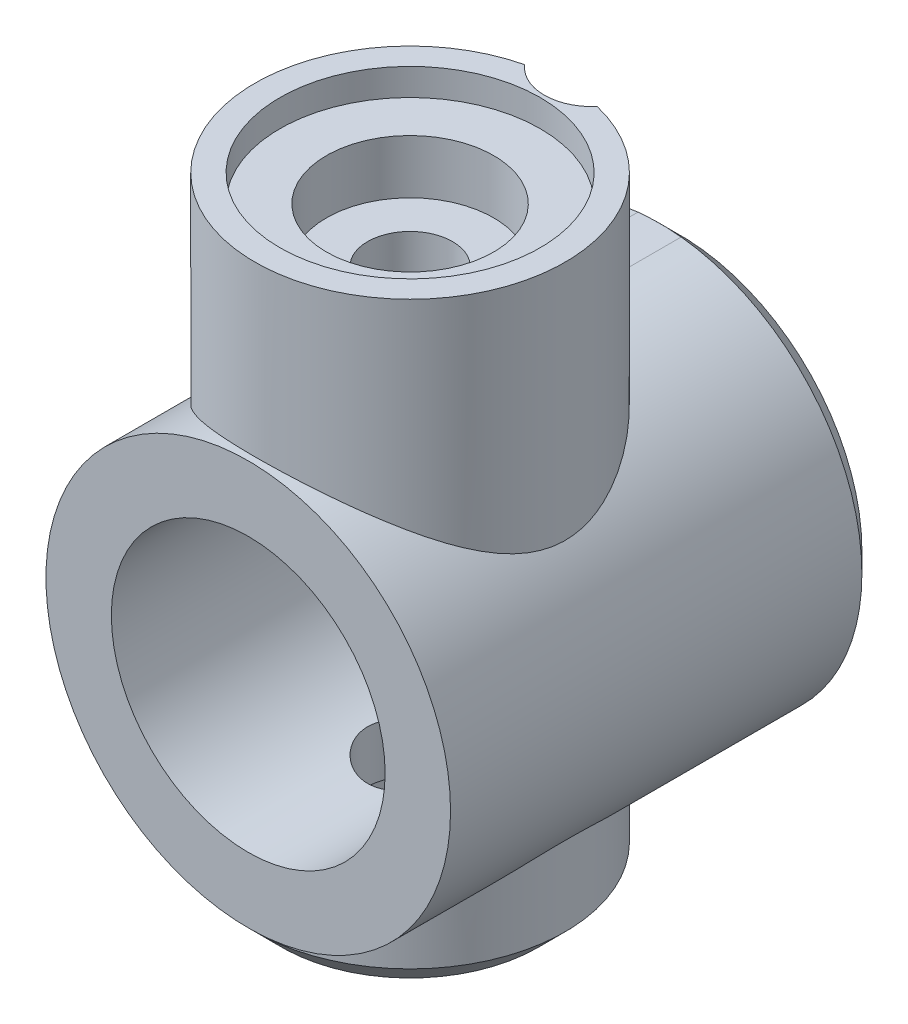
SolidWorks part; units mm, degrees
material "ABS"
ref_plane "前视基准面" through (0, 0, 0) normal (0, 0, 1) x (1, 0, 0)
ref_plane "上视基准面" through (0, 0, 0) normal (0, 1, 0) x (1, 0, 0)
ref_plane "右视基准面" through (0, 0, 0) normal (1, 0, 0) x (0, 0, -1)
other "Configuration Table"
sketch "草图1" plane through (0, 0, 0) normal (0, 1, 0) x (1, 0, 0)
  line L0 (0, 0) -> (55, 0)
  line L1 (0, 0) -> (0, -7)
  line L2 (55, 0) -> (55, -7)
  arc A0 (0, -7) -> (55, -7) centre (27.5, -7) ccw
  dimension "D1" = 55
  dimension "D2" = 7
  dimension "D3" = 7
extrude "凸台-拉伸1" add sketch "草图1" along normal blind 45
sketch "草图5" plane through (0, 0, 0) normal (0, 0, -1) x (-1, 0, 0)
  line L0 (-55, 45) -> (0, 0) construction
  line L1 (-55, 0) -> (0, 45) construction
  circle A0 centre (-27.5, 22.5) radius 7.9
  dimension "D1" = 15.8
extrude "凸台-拉伸3" add sketch "草图5" along normal blind 45
chamfer "倒角5" distance 8 angle 45 6 edges at (0, 45, 3.5) (55, 45, 3.5) (27.5, 45, 34.5) (0, 0, 3.5) (55, 0, 3.5) (27.5, 0, 34.5)
chamfer "倒角6" distance 2 angle 45 8 edges at (4, 4, 0) (27.5, 0, 0) (51, 4, 0) (55, 22.5, 0) (51, 41, 0) (27.5, 45, 0) (4, 41, 0) (0, 22.5, 0)
fillet "圆角5" radius 3 1 edges at (19.6, 22.5, -45)
fillet "圆角6" radius 2 1 edges at (19.6, 22.5, 0)
sketch "草图7" plane through (0, 0, 0) normal (0, 0, -1) x (-1, 0, 0)
  circle A0 centre (-27.5, 22.5) radius 10.15
  circle A1 centre (-27.5, 22.5) radius 15
  dimension "D1" = 20.3
  dimension "D2" = 30
extrude "凸台-拉伸4" add sketch "草图7" along normal blind 45
sketch "草图6" plane through (0, 0, 0) normal (0, 1, 0) x (1, 0, 0)
  line L0 (27.5, 0) -> (27.5, 8.5) construction
  line L1 (8.8284, 0) -> (46.1716, 0) construction
  line L2 (27.5, 8.5) -> (27.5, 25) construction
  line L3 (27.5, 25) -> (27.5, 38.5) construction
  circle A0 centre (27.5, 8.5) radius 1.6
  circle A1 centre (27.5, 25) radius 3.1
  circle A2 centre (27.5, 38.5) radius 1.6
  dimension "D4" = 3.2
  dimension "D5" = 6.2
  dimension "D6" = 3.2
  dimension "D1" = 8.5
  dimension "D2" = 16.5
  dimension "D3" = 13.5
extrude "切除-拉伸4" cut sketch "草图6" along normal through all
sketch "草图10" plane through (0, 0, 0) normal (0, 1, 0) x (1, 0, 0)
  circle A0 centre (27.5, 25) radius 11.5
  dimension "D1" = 23
extrude "凸台-拉伸5" add sketch "草图10" along normal blind 50
fillet "圆角9" radius 5 1 edges at (42.5, 22.5, 0)
sketch "草图11" plane through (0, 0, -45) normal (0, 0, -1) x (-1, 0, 0)
  circle A0 centre (-27.5, 22.5) radius 7.9
  circle A1 centre (-27.5, 22.5) radius 10.15
  dimension "D1" = 15.8
  dimension "D2" = 20.3
extrude "切除-拉伸6" cut sketch "草图11" against normal blind 40
sketch "草图12" plane through (0, 0, 0) normal (0, -1, 0) x (1, 0, 0)
  circle A0 centre (27.5, -25) radius 3.15
  dimension "D1" = 6.3
extrude "切除-拉伸7" cut sketch "草图12" against normal blind 40
chamfer "倒角9" distance 1.5 angle 45 2 edges at (17.35, 22.5, -45) (12.5, 22.5, -45)
sketch "草图13" plane through (0, 50, 0) normal (0, 1, 0) x (1, 0, 0)
  circle A0 centre (27.5, 25) radius 6.2
  dimension "D1" = 12.4
extrude "切除-拉伸8" cut sketch "草图13" against normal blind 6
sketch "草图15" plane through (0, 0, 0) normal (0, -1, 0) x (1, 0, 0)
  circle A0 centre (27.5, -25) radius 11.5
  dimension "D1" = 23
sketch "草图19" plane through (0, 0, 0) normal (0, 0, -1) x (-1, 0, 0)
  circle A0 centre (-27.5, 22.5) radius 36.5929
extrude "切除-拉伸12" cut sketch "草图19" against normal through all
sketch "草图20" plane through (0, 0, 0) normal (0, 0, 1) x (1, 0, 0)
  circle A0 centre (27.5, 22.5) radius 20
extrude "切除-拉伸13" cut sketch "草图20" against normal blind 13
sketch "草图21" plane through (0, 0, -13) normal (0, 0, 1) x (1, 0, 0)
  circle A0 centre (27.5, 22.5) radius 7.9
extrude "切除-拉伸14" cut sketch "草图21" against normal through all contours A0
sketch "草图22" plane through (0, 0, -45) normal (0, 0, -1) x (-1, 0, 0)
  line L1 (-29.5325, 7.3617) -> (-25.4675, 7.3617)
  line L2 (-29.5325, 7.3617) -> (-29.5325, 7.6383)
  line L3 (-29.5325, 7.6383) -> (-25.4675, 7.6383)
  line L4 (-25.4675, 7.3617) -> (-25.4675, 7.6383)
  line L5 (-29.5325, 7.3617) -> (-25.4675, 7.6383) construction
  line L6 (-29.5325, 7.6383) -> (-25.4675, 7.3617) construction
  line L7 (-29.1, 37.5856) -> (-25.9, 37.5856)
  line L8 (-29.1, 37.5856) -> (-29.1, 37.4144)
  line L9 (-29.1, 37.4144) -> (-25.9, 37.4144)
  line L10 (-25.9, 37.5856) -> (-25.9, 37.4144)
  line L11 (-29.1, 37.5856) -> (-25.9, 37.4144) construction
  line L12 (-29.1, 37.4144) -> (-25.9, 37.5856) construction
  arc A0 (-39, 12.8693) -> (-16, 12.8693) centre (-27.5, 22.5) ccw construction
  arc A1 (-16, 32.1307) -> (-39, 32.1307) centre (-27.5, 22.5) ccw construction
  circle A2 centre (-27.5, 22.5) radius 15 construction
  point P0 (-27.5, 7.5)
  point P8 (-27.5, 37.5)
extrude "切除-拉伸15" cut sketch "草图22" against normal blind 8.5
extrude "切除-拉伸16" cut sketch "草图15" against normal blind 5
sketch "草图23" plane through (0, 5, 0) normal (0, -1, 0) x (1, 0, 0)
  circle A0 centre (27.5, -25) radius 5.2
  dimension "D1" = 10.4
extrude "切除-拉伸17" cut sketch "草图23" against normal blind 4
chamfer "倒角10" distance 2 angle 45 1 edges at (27.5, 5, -36.5)
sketch "草图24" plane through (0, 44, 0) normal (0, 1, 0) x (1, 0, 0)
  circle A0 centre (27.5, 25) radius 3.15
  circle A1 centre (27.5, 25) radius 11.5 construction
  dimension "D1" = 6.3
extrude "切除-拉伸18" cut sketch "草图24" against normal through all
sketch "草图25" plane through (0, 50, 0) normal (0, 1, 0) x (1, 0, 0)
  circle A0 centre (27.5, 25) radius 9.65
  circle A1 centre (27.5, 25) radius 11.5 construction
  dimension "D1" = 19.3
extrude "切除-拉伸19" cut sketch "草图25" against normal blind 2
sketch "草图26" plane through (0, 37.4144, 0) normal (0, 1, 0) x (1, 0, 0)
  circle A0 centre (27.5, 38.5) radius 3.55
  dimension "D1" = 7.1
extrude "切除-拉伸20" cut sketch "草图26" along normal blind 14
sketch "草图27" plane through (0, 7.6383, 0) normal (0, -1, 0) x (1, 0, 0)
  circle A0 centre (27.5, -38.5) radius 3.55
  dimension "D1" = 7.1
extrude "切除-拉伸21" cut sketch "草图27" along normal blind 5
